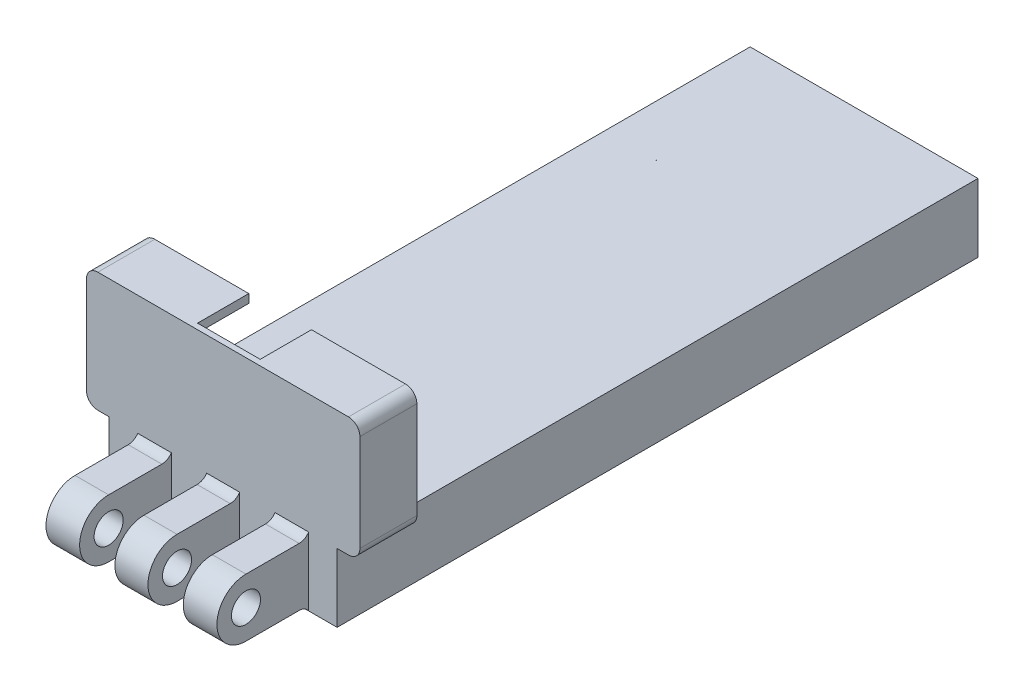
SolidWorks part; units mm, degrees
ref_plane "Front Plane" through (0, 0, 0) normal (0, 0, 1) x (1, 0, 0)
ref_plane "Top Plane" through (0, 0, 0) normal (0, 1, 0) x (1, 0, 0)
ref_plane "Right Plane" through (0, 0, 0) normal (1, 0, 0) x (0, 0, -1)
sketch "Sketch1" plane through (0, 0, 0) normal (0, 0, 1) x (1, 0, 0)
  line L0 (0, 0) -> (0, 31.117) construction
  line L4 (-20, -6) -> (20, -6)
  line L5 (-20, -6) -> (-20, 6)
  line L6 (-20, 6) -> (20, 6)
  line L7 (20, -6) -> (20, 6)
  line L8 (-20, -6) -> (20, 6) construction
  line L9 (-20, 6) -> (20, -6) construction
  circle A0 centre (11, 0) radius 4.25
  circle A1 centre (-11, 0) radius 4.25
  dimension "D1" = 8.5
  dimension "D3" = 12
  dimension "D2" = 22
  dimension "D4" = 40
extrude "Boss-Extrude1" add sketch "Sketch1" along normal blind 1 and the other way blind 112
sketch "Sketch3" plane through (0, 0, 0) normal (1, 0, 0) x (0, 0, -1)
  line L0 (-12, -5.1) -> (-1, -5.1)
  line L2 (-12, 5.1) -> (-1, 5.1)
  line L3 (-1, 5.1) -> (-1, -5.1)
  line L4 (-1, -6) -> (-1, 6) construction
  circle A1 centre (-12, 0) radius 2.55
  arc A2 (-12, 5.1) -> (-12, -5.1) centre (-12, 0) ccw
  dimension "D1" = 5.1
  dimension "D2" = 5.1
  dimension "D3" = 12
extrude "Boss-Extrude2" add sketch "Sketch3" along normal mid plane 30
extrude "Cut-Extrude1" cut sketch "Sketch3<2>" against normal blind 6.2 from offset 2.9 offset against normal yes
sketch "Sketch3<2>" plane through (0, 0, 0) normal (1, 0, 0) x (0, 0, -1) same geometry as "Sketch3"
mirror "Mirror1" about plane through (0, 0, 0) normal (1, 0, 0) of "Cut-Extrude1"
sketch "Sketch5" plane through (0, 0, 1) normal (0, 0, 1) x (1, 0, 0)
  circle A0 centre (-11, 0) radius 4.25
  arc A1 (-9.1, -3.8016) -> (-9.1, 3.8016) centre (-11, 0) ccw construction
  circle A2 centre (11, 0) radius 4.25
  arc A3 (9.1, 3.8016) -> (9.1, -3.8016) centre (11, 0) ccw construction
extrude "Boss-Extrude3" add sketch "Sketch5" against normal blind 3
sketch "Sketch6" plane through (0, 0, -112) normal (0, 0, -1) x (-1, 0, 0)
  line L0 (-20, 6) -> (20, 6) construction
  line L7 (-25, 6) -> (25, 6)
  line L8 (-25, 6) -> (-25, 30)
  line L9 (-25, 30) -> (25, 30)
  line L10 (25, 6) -> (25, 30)
  point P5 (0, 30)
  dimension "D2" = 50
  dimension "D1" = 24
chamfer "Chamfer3" distance 0.5 angle 45 6 edges at (15.25, 0, -112) (20, 0, -112) (-20, 0, -112) (0, -6, -112) (-15.25, 0, -112) (0, 6, -112)
fillet "Fillet3" radius 2 6 edges at (-12.05, -5.1, 1) (0, -5.1, 1) (12.05, -5.1, 1) (-12.05, 5.1, 1) (0, 5.1, 1) (12.05, 5.1, 1)
ref_plane "Plane1" through (0, 0, 1) normal (0, 0, -1) x (-1, 0, 0)
sketch "Sketch12" plane through (0, 0, 1) normal (0, 0, -1) x (-1, 0, 0)
  circle A0 centre (11, 0) radius 4.05
  circle A1 centre (-11, 0) radius 4.05
extrude "Boss-Extrude9" add sketch "Sketch12" along normal blind 100
sketch "Sketch18" plane through (0, 0, 1) normal (0, 0, -1) x (-1, 0, 0)
  line L5 (-24, 27) -> (24, 27)
  line L6 (-24, 27) -> (-24, 6)
  line L7 (-24, 6) -> (24, 6)
  line L8 (24, 27) -> (24, 6)
  line L9 (-24, 27) -> (24, 6) construction
  line L10 (-24, 6) -> (24, 27) construction
  line L12 (-20, 6) -> (20, 6) construction
  point P4 (0, 16.5)
  dimension "D3" = 21
  dimension "D4" = 48
extrude "Boss-Extrude11" add sketch "Sketch18" along normal blind 10
fillet "Fillet10" radius 2 4 edges at (24, 27, -4) (24, 6, -4) (-24, 6, -4) (-24, 27, -4)
sketch "Sketch20" plane through (0, 0, -9) normal (0, 0, -1) x (-1, 0, 0)
  line L2 (-22.5, 24.5) -> (-22.5, 6)
  line L3 (-22.5, 6) -> (22.5, 6)
  line L4 (22.5, 24.5) -> (22.5, 6)
  line L5 (-24, 27) -> (-24, 6) construction
  line L7 (-24, 6) -> (24, 6) construction
  line L8 (24, 27) -> (24, 6) construction
  line L14 (5.5, 25.5) -> (21.5, 25.5)
  line L16 (-21.5, 25.5) -> (-5.5, 25.5)
  line L17 (-5.5, 25.5) -> (-5.5, 27)
  line L18 (22, 27) -> (-22, 27) construction
  line L19 (-5.5, 27) -> (5.5, 27)
  line L20 (5.5, 27) -> (5.5, 25.5)
  arc A1 (-22.5, 24.5) -> (-21.5, 25.5) centre (-21.5, 24.5) cw
  arc A2 (22.5, 24.5) -> (21.5, 25.5) centre (21.5, 24.5) ccw
  point P6 (0, 27)
  dimension "D4" = 1
  dimension "D6" = 1
  dimension "D1" = 1.5
  dimension "D2" = 1.5
  dimension "D3" = 1.5
  dimension "D5" = 11
  dimension "D7" = 1.5
extrude "Cut-Extrude8" cut sketch "Sketch20" against normal blind 9
sketch "Sketch22" plane through (0, 0, -99) normal (0, 0, -1) x (-1, 0, 0)
  line L0 (15.75, 0) -> (6.25, 0)
  line L1 (-6.25, 0) -> (-15.75, 0)
  arc A1 (-15.75, 0) -> (-6.25, 0) centre (-11, 0) ccw
  arc A2 (6.25, 0) -> (15.75, 0) centre (11, 0) ccw
extrude "Boss-Extrude12" add sketch "Sketch22" along normal blind 13
